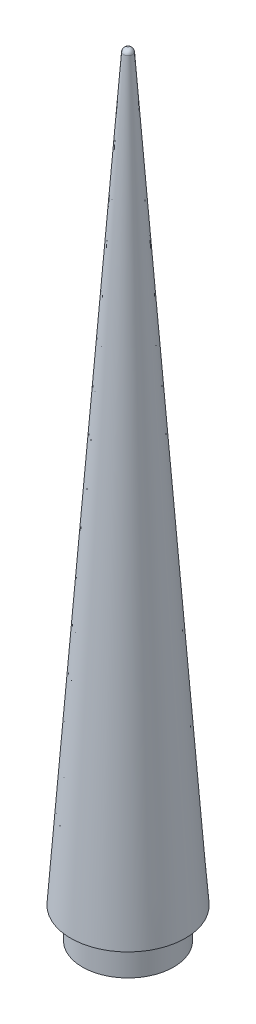
SolidWorks part; units mm, degrees
material "6061-T6 (SS)"
ref_plane "Front Plane" through (0, 0, 0) normal (0, 0, 1) x (1, 0, 0)
ref_plane "Top Plane" through (0, 0, 0) normal (0, 1, 0) x (1, 0, 0)
ref_plane "Right Plane" through (0, 0, 0) normal (1, 0, 0) x (0, 0, -1)
sketch "Sketch1" plane through (0, 0, 0) normal (0, 1, 0) x (1, 0, 0)
  circle A0 centre (0, 0) radius 9.398
  dimension "D1" = 18.796
extrude "Boss-Extrude1" add sketch "Sketch1" along normal blind 6.35
sketch "Sketch2" plane through (0, 0, 0) normal (0, 0, 1) x (1, 0, 0)
  line L0 (11.811, 6.35) -> (0.889, 159.258)
  line L1 (0, 159.258) -> (0, 6.35)
  line L2 (9.398, 6.35) -> (-9.398, 6.35) construction
  line L3 (0, 6.35) -> (11.811, 6.35)
  line L4 (26.8574, -204.2989) -> (11.811, 6.35) construction
  line L5 (0, 159.258) -> (0.889, 159.258)
  dimension "D1" = 0.889
ref_axis "Axis1" through (0, 6.35, 0) along (0, -1, 0)
revolve "Revolve1" add sketch "Sketch2" angle 360 about L1
fillet "Fillet1" radius 0.889 1 edges at (0, 159.258, 0.889)
